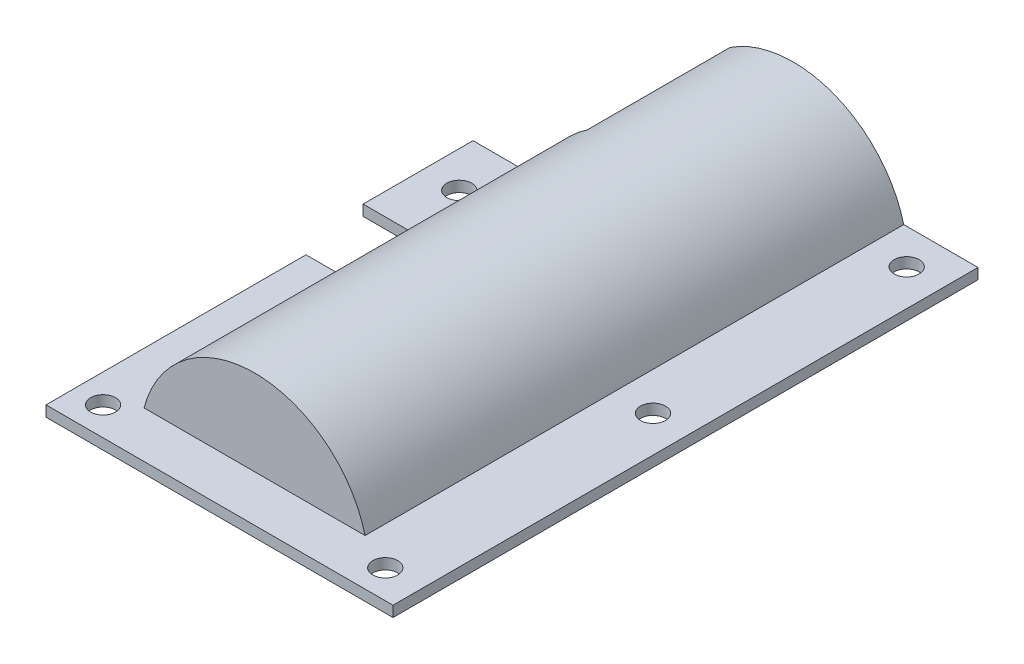
SolidWorks part; units mm, degrees
ref_plane "Front Plane" through (0, 0, 0) normal (0, 0, 1) x (1, 0, 0)
ref_plane "Top Plane" through (0, 0, 0) normal (0, 1, 0) x (1, 0, 0)
ref_plane "Right Plane" through (0, 0, 0) normal (1, 0, 0) x (0, 0, -1)
sketch "Sketch1" plane through (0, 0, 0) normal (0, 0, 1) x (1, 0, 0)
  line L0 (-16, 0) -> (-14, 0)
  line L1 (-15.4919, 4) -> (-13.4164, 4)
  line L2 (-26.231, 0) -> (35.5744, 0) construction
  line L3 (-26.231, 4) -> (35.5744, 4) construction
  line L4 (13.4164, 4) -> (15.4919, 4)
  arc A0 (13.4164, 4) -> (-13.4164, 4) centre (0, 0) ccw
  arc A1 (15.4919, 4) -> (-15.4919, 4) centre (0, 0) ccw
  circle A2 centre (0, 0) radius 16 construction
  circle A3 centre (0, 0) radius 14 construction
  dimension "D1" = 2
  dimension "D2" = 4
extrude "Boss-Extrude1" add sketch "Sketch1" along normal blind 72.5 contours L4 A1 L1 A0 region at (0, 15.6677, 0)
sketch "Sketch2" plane through (0, 0, 72.5) normal (0, 0, 1) x (1, 0, 0)
  line L0 (-15.4919, 4) -> (15.4919, 4)
  arc A0 (-15.4919, 4) -> (15.4919, 4) centre (0, 0) cw
extrude "Boss-Extrude2" add sketch "Sketch2" along normal blind 1.5
sketch "Sketch3" plane through (0, 0, 0) normal (0, 0, -1) x (-1, 0, 0)
  line L0 (-15.4919, 4) -> (15.4919, 4)
  arc A0 (-15.4919, 4) -> (15.4919, 4) centre (0, 0) cw
extrude "Boss-Extrude3" add sketch "Sketch3" along normal blind 1.5
sketch "Sketch4" plane through (0, 4, 0) normal (0, -1, 0) x (1, 0, 0)
  line L0 (-22.74, 80.5) -> (-22.74, 44.06)
  line L4 (-13.4164, 72.5) -> (13.4164, 72.5) construction
  line L6 (-24.89, -1.5) -> (25.9, -1.5)
  line L9 (25.9, 80.5) -> (-22.74, 80.5)
  line L10 (0, 62.7452) -> (0, 48.669)
  line L11 (25.9, 80.5) -> (25.9, -1.5)
  line L12 (-24.89, 44.06) -> (-24.89, -1.5)
  line L13 (-22.74, 44.06) -> (-24.89, 44.06)
  line L14 (-13.4164, 72.5) -> (-13.4164, 0)
  line L15 (-13.4164, 0) -> (13.4164, 0)
  line L16 (13.4164, 0) -> (13.4164, 72.5)
  line L17 (13.4164, 72.5) -> (-13.4164, 72.5)
  circle A9 centre (20.82, 76.5) radius 1.75
  circle A10 centre (20.82, 38.98) radius 1.75
  circle A11 centre (20.82, 3.42) radius 1.75
  circle A12 centre (-18.74, 76.5) radius 1.75
  circle A13 centre (-19.81, 25.5) radius 1.75
  line M15 (-15.4919, -1.5) -> (15.4919, -1.5)
  line M16 (15.4919, -1.5) -> (15.4919, 74)
  line M17 (15.4919, 74) -> (-15.4919, 74)
  line M18 (-15.4919, 74) -> (-15.4919, -1.5)
  line M19 (13.4164, 72.5) -> (13.4164, 0)
  line M20 (13.4164, 0) -> (-13.4164, 0)
  line M21 (-13.4164, 0) -> (-13.4164, 72.5)
  line M22 (-13.4164, 72.5) -> (13.4164, 72.5)
  dimension "D1" = 20.82
  dimension "D3" = 3.5
  dimension "D4" = 5.08
  dimension "D5" = 37.52
  dimension "D7" = 39.56
  dimension "D6" = 73.08
  dimension "D11" = 19.81
  dimension "D2" = 4
  dimension "D8" = 4
  dimension "D9" = 4
  dimension "D10" = 36.44
  dimension "D12" = 51
  dimension "D13" = 5.08
extrude "Boss-Extrude4" add sketch "Sketch4" along normal blind 1.5 contours A9 M18 M17 M16 | M18 M15 M16 M17 M22 M19 M20 M21 region at (1.58, 4, 79.5354) region at (0, 4, -0.6839)
sketch "Sketch5" plane through (0, 2.5, 0) normal (0, -1, 0) x (1, 0, 0)
  line L0 (-24.89, -1.5) -> (-24.89, 18.5)
  line L1 (-24.89, 44.06) -> (-24.89, -1.5) construction
  line L2 (-24.89, -1.5) -> (-8.89, -1.5)
  line L3 (-24.89, -1.5) -> (25.9, -1.5) construction
  line L4 (-8.89, -1.5) -> (-8.89, 18.5)
  line L5 (-8.89, 18.5) -> (-24.89, 18.5)
  dimension "D1" = 20
  dimension "D2" = 16
extrude "Cut-Extrude1" cut sketch "Sketch5" against normal blind 15
sketch "Sketch6" plane through (0, 2.5, 0) normal (0, -1, 0) x (1, 0, 0)
  line L0 (-24.89, 44.06) -> (-13.4164, 44.06)
  line L1 (-13.4164, 44.06) -> (-13.4164, 33.9)
  line L2 (-24.89, 44.06) -> (-24.89, 33.9)
  line L3 (-13.4164, 33.9) -> (-24.89, 33.9)
  line L4 (-13.4164, 18.5) -> (-13.4164, 72.5) construction
  line L6 (-24.89, 44.06) -> (-24.89, 18.5) construction
extrude "Cut-Extrude2" cut sketch "Sketch6" against normal blind 10
